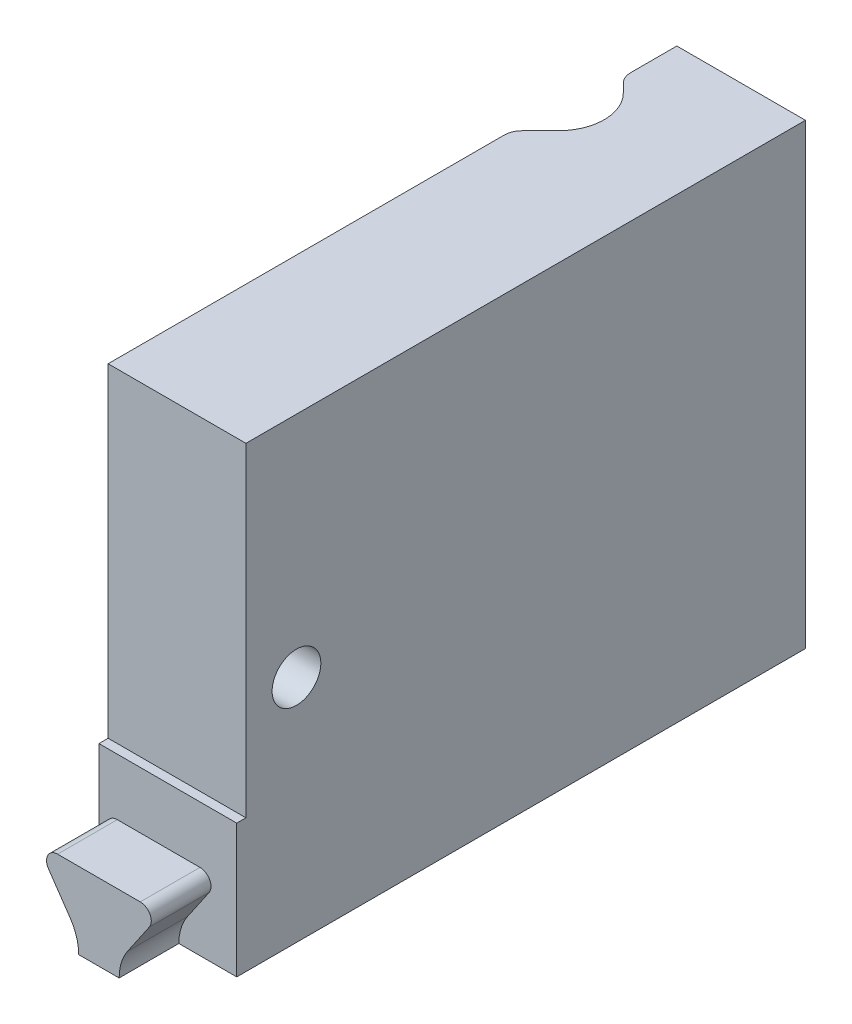
SolidWorks part; units mm, degrees
ref_plane "Front Plane" through (0, 0, 0) normal (0, 0, 1) x (1, 0, 0)
ref_plane "Top Plane" through (0, 0, 0) normal (0, 1, 0) x (1, 0, 0)
ref_plane "Right Plane" through (0, 0, 0) normal (1, 0, 0) x (0, 0, -1)
sketch "Sketch1" plane through (0, 0, 0) normal (0, 0, 1) x (1, 0, 0)
  line L1 (0, 0) -> (-15, 0)
  line L2 (0, 0) -> (0, 14.5)
  line L4 (-15, 0) -> (-15, 14.5)
  line L9 (0, 14.5) -> (-15, 14.5)
  dimension "D2" = 15
  dimension "D3" = 14.5
extrude "Offset" add sketch "Sketch1" along normal blind 1
sketch "Sketch13" plane through (0, 0, 1) normal (0, 0, 1) x (1, 0, 0)
  line L4 (-10.7, 0) -> (-6.3, 0)
  line L7 (-11.6264, 2.9936) -> (-13.9903, 6.4472)
  line L8 (-13, 8.325) -> (-4, 8.325)
  line L12 (-3.0097, 6.4472) -> (-5.3736, 2.9936)
  line L13 (-11.6264, 2.9936) -> (-13.9903, 6.4472)
  line L14 (-13, 8.325) -> (-4, 8.325)
  line L15 (-3.0097, 6.4472) -> (-5.3736, 2.9936)
  arc A8 (-10.7, 0) -> (-11.6264, 2.9936) centre (-16, 0) ccw
  arc A9 (-13, 8.325) -> (-13.9903, 6.4472) centre (-13, 7.125) ccw
  arc A10 (-3.0097, 6.4472) -> (-4, 8.325) centre (-4, 7.125) ccw
  arc A11 (-5.3736, 2.9936) -> (-6.3, 0) centre (-1, 0) ccw
  arc A16 (-10.7, 0) -> (-11.6264, 2.9936) centre (-16, 0) ccw
  arc A17 (-13, 8.325) -> (-13.9903, 6.4472) centre (-13, 7.125) ccw
  arc A18 (-3.0097, 6.4472) -> (-4, 8.325) centre (-4, 7.125) ccw
  arc A19 (-5.3736, 2.9936) -> (-6.3, 0) centre (-1, 0) ccw
  dimension "D1" = 0.3
extrude "Dovetail" add sketch "Sketch13" along normal up to surface (6.5 mm away)
sketch "Sketch5" plane through (0, 0, 0) normal (0, 0, -1) x (-1, 0, 0)
  line L0 (15, 14.5) -> (15, 0) construction
  line L1 (0, 0) -> (15, 0)
  line L2 (0, 0) -> (0, 49.8)
  line L3 (0, 49.8) -> (15, 49.8)
  line L4 (15, 0) -> (15, 49.8)
  line L5 (0, 0) -> (15, 49.8) construction
  line L6 (0, 49.8) -> (15, 0) construction
  line L7 (75.6068, 50) -> (-45.3932, 50) construction
  point P4 (7.5, 24.9)
  dimension "D1" = 0.2
extrude "Base" add sketch "Sketch5" along normal blind 15
sketch "Sketch6" plane through (0, 0, 0) normal (0, -1, 0) x (1, 0, 0)
  line L2 (0, -15) -> (-15, -15) construction
  line L3 (0, -15) -> (-15, -15)
  line L8 (-15, -15) -> (-15, -43.1005)
  line L12 (-14.4142, -44.5147) -> (-12.4645, -46.4645)
  line L13 (-12.4645, -53.5355) -> (-13.4142, -54.4853)
  line L14 (-14, -55.8995) -> (-14, -60.8995)
  line L15 (-14, -60.8995) -> (0, -60.8995)
  line L18 (0, -60.8995) -> (0, -15)
  line L20 (0, 1) -> (0, -15) construction
  arc A5 (-12.4645, -46.4645) -> (-12.4645, -53.5355) centre (-16, -50) cw
  arc A6 (-13.4142, -54.4853) -> (-14, -55.8995) centre (-12, -55.8995) ccw
  arc A7 (-15, -43.1005) -> (-14.4142, -44.5147) centre (-13, -43.1005) ccw
  point P15 (-8.9289, -50)
  dimension "D1" = 5
  dimension "D2" = 2
  dimension "D3" = 35
  dimension "D4" = 1
  dimension "D5" = 1
  dimension "D6" = 5
extrude "Gripping" add sketch "Sketch6" against normal up to surface (49.8 mm away) up to face at (-7.5, 49.8, -7.5)
sketch "Sketch11" plane through (-15, 0, 0) normal (-1, 0, 0) x (0, 0, 1)
  line L1 (13, 50) -> (13, 0) construction
  line L7 (-11, 50) -> (7.5, 50) construction
  line L8 (-11, 0) -> (7.5, 0) construction
  circle A7 centre (-5.5, 25) radius 2.65 construction
  circle A8 centre (-5.5, 25) radius 2.65
  dimension "D1" = 5.3
extrude "ShaftHole" cut sketch "Sketch11" against normal through all both and the other way through all
